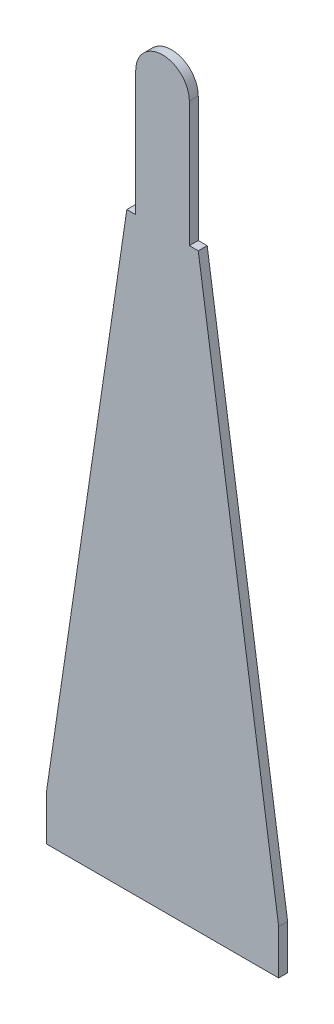
SolidWorks part; units mm, degrees
ref_plane "Ebene vorne" through (0, 0, 0) normal (0, 0, 1) x (1, 0, 0)
ref_plane "Ebene oben" through (0, 0, 0) normal (0, 1, 0) x (1, 0, 0)
ref_plane "Ebene rechts" through (0, 0, 0) normal (1, 0, 0) x (0, 0, -1)
sketch "Skizze1" plane through (0, 0, 0) normal (0, 0, 1) x (1, 0, 0)
  line L0 (-40, 660) -> (-130, 50)
  line L1 (-263.5092, 660) -> (296.6943, 660) construction
  line L2 (0, 800) -> (0, 0)
  line L3 (-30, 800) -> (-30, 660)
  line L4 (-40, 660) -> (-30, 660)
  line L5 (0, 800) -> (0, 830)
  line L7 (-130, 0) -> (-130, 50)
  line L10 (40, 660) -> (30, 660)
  line L12 (-130, 0) -> (0, 0)
  arc A2 (0, 830) -> (-30, 800) centre (0, 800) ccw
  point P4 (0, 660)
  point P8 (-40, 660)
  dimension "D2" = 30
  dimension "D5" = 50
  dimension "D6" = 130
  dimension "D1" = 800
  dimension "D3" = 140
  dimension "D4" = 40
extrude "Aufsatz-Linear austragen1" add sketch "Skizze1" along normal blind 10 contours L2 L12 L7 L0 L4 L3 A2 L5
mirror "Spiegeln1" about plane through (0, 800, 10) normal (1, 0, 0) of "Aufsatz-Linear austragen1"
